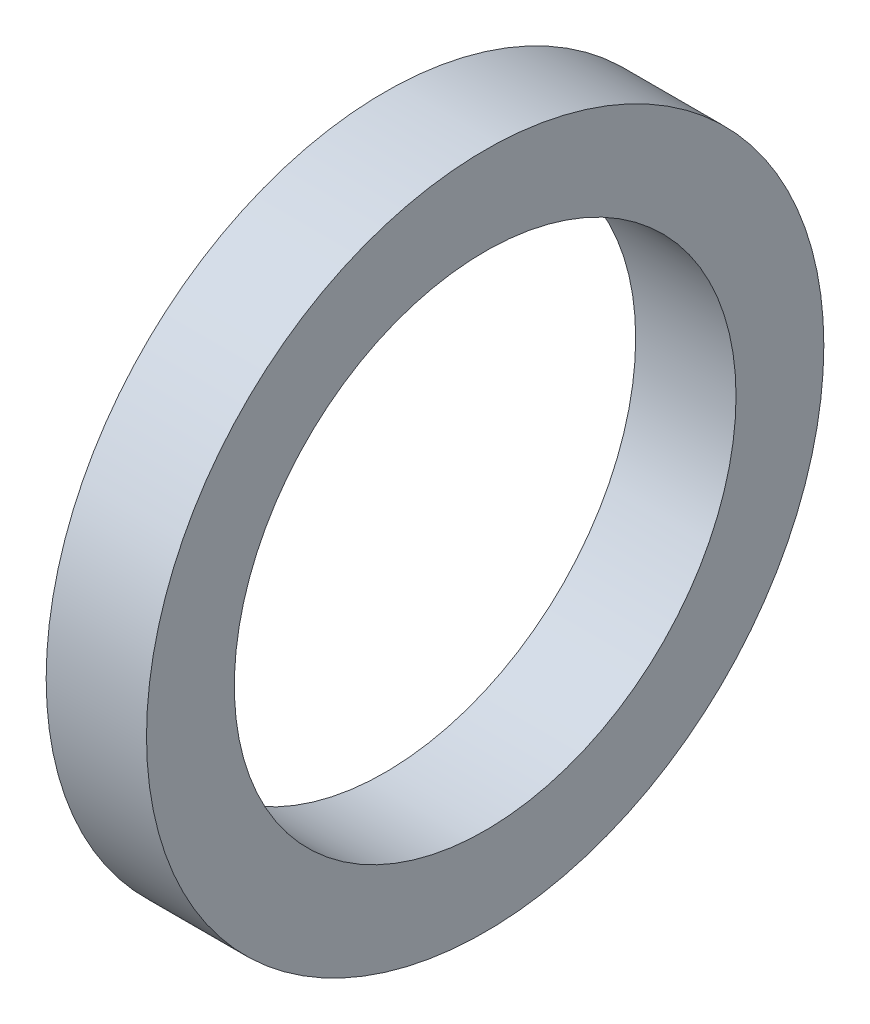
SolidWorks part; units mm, degrees
ref_plane "前视基准面" through (0, 0, 0) normal (0, 0, 1) x (1, 0, 0)
ref_plane "上视基准面" through (0, 0, 0) normal (0, 1, 0) x (1, 0, 0)
ref_plane "右视基准面" through (0, 0, 0) normal (1, 0, 0) x (0, 0, -1)
sketch "草图1" plane through (0, 0, 0) normal (1, 0, 0) x (0, 0, -1)
  circle A0 centre (0, 0) radius 13.5
  circle A1 centre (0, 0) radius 10
  dimension "D1" = 27
  dimension "D2" = 20
extrude "凸台-拉伸1" add sketch "草图1" along normal mid plane 4
move or copy body "实体-移动/复制1" [suppressed] bodies to move or copy 101
